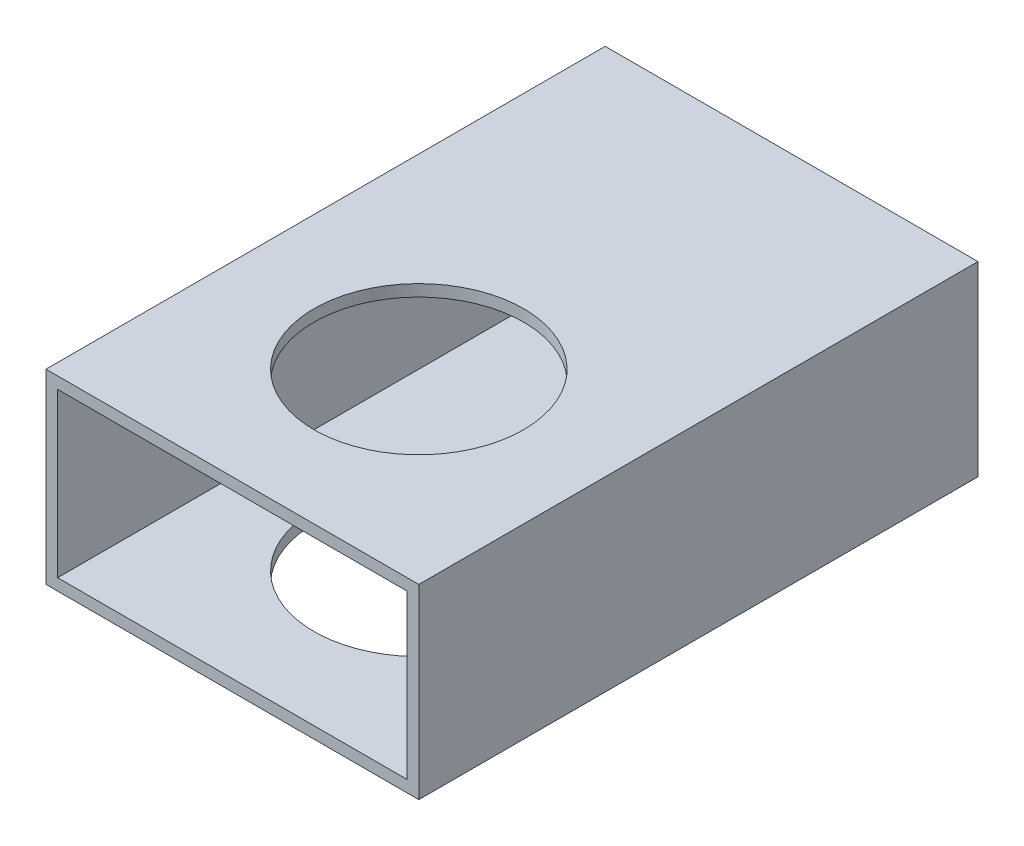
SolidWorks part; units mm, degrees
ref_plane "Front Plane" through (0, 0, 0) normal (0, 0, 1) x (1, 0, 0)
ref_plane "Top Plane" through (0, 0, 0) normal (0, 1, 0) x (1, 0, 0)
ref_plane "Right Plane" through (0, 0, 0) normal (1, 0, 0) x (0, 0, -1)
sketch "Sketch1" plane through (0, 0, 0) normal (0, 0, 1) x (1, 0, 0)
  line L1 (23.8125, -11.1125) -> (-23.8125, -11.1125)
  line L2 (23.8125, -11.1125) -> (23.8125, 11.1125)
  line L3 (23.8125, 11.1125) -> (-23.8125, 11.1125)
  line L4 (-23.8125, -11.1125) -> (-23.8125, 11.1125)
  line L5 (23.8125, -11.1125) -> (-23.8125, 11.1125) construction
  line L6 (23.8125, 11.1125) -> (-23.8125, -11.1125) construction
  line L7 (25.4, -12.7) -> (-25.4, -12.7)
  line L8 (25.4, -12.7) -> (25.4, 12.7)
  line L9 (25.4, 12.7) -> (-25.4, 12.7)
  line L10 (-25.4, -12.7) -> (-25.4, 12.7)
  line L11 (25.4, -12.7) -> (-25.4, 12.7) construction
  line L12 (25.4, 12.7) -> (-25.4, -12.7) construction
  point P0 (0, 0)
  point P6 (0, 0)
  point P11 (12.4812, -13.4339)
  dimension "D1" = 50.8
  dimension "D2" = 25.4
  dimension "D3" = 1.5875
  dimension "D4" = 1.5875
extrude "Boss-Extrude1" add sketch "Sketch1" along normal blind 76.2
sketch "Sketch2" plane through (0, -12.7, 0) normal (0, -1, 0) x (1, 0, 0)
  line L0 (0, 0) -> (0, 50.8) construction
  line L1 (-25.4, 0) -> (25.4, 0) construction
  circle A0 centre (0, 50.8) radius 14.2875
  dimension "D2" = 28.575
  dimension "D1" = 50.8
extrude "Cut-Extrude1" cut sketch "Sketch2" against normal through all
